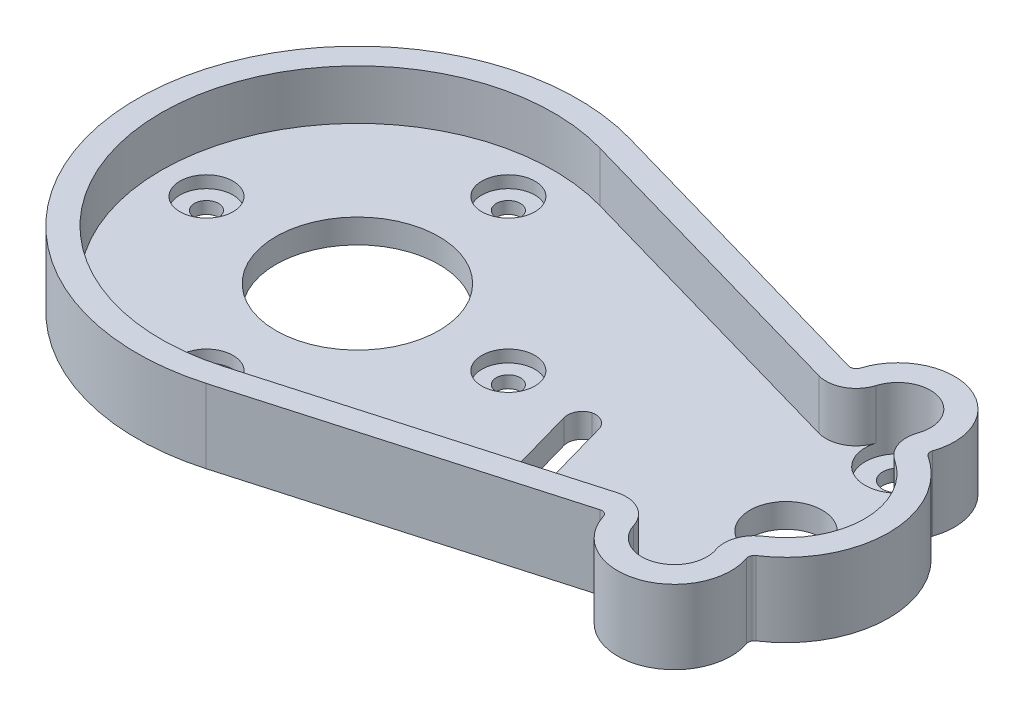
SolidWorks part; units mm, degrees
ref_plane "Front Plane" through (0, 0, 0) normal (0, 0, 1) x (1, 0, 0)
ref_plane "Top Plane" through (0, 0, 0) normal (0, 1, 0) x (1, 0, 0)
ref_plane "Right Plane" through (0, 0, 0) normal (1, 0, 0) x (0, 0, -1)
sketch "Sketch1" plane through (0, 0, 0) normal (0, 1, 0) x (1, 0, 0)
  line L0 (0, 73.0538) -> (0, -65.1274) construction
  line L1 (35.5, 6.365) -> (-28.5632, 24.502) construction
  line L2 (-70.6215, 0) -> (67.3742, 0) construction
  line L3 (35.5, -6.365) -> (-28.5632, -24.502) construction
  line L4 (4.5177, -15.1364) -> (0.1592, 0.2585)
  line L5 (0.1592, 0.2585) -> (4.6815, 1.5388)
  line L6 (4.6815, 1.5388) -> (9.04, -13.8561)
  line L7 (9.04, -13.8561) -> (9.5848, -15.7805)
  line L8 (9.5848, -15.7805) -> (5.0625, -17.0608)
  line L9 (5.0625, -17.0608) -> (4.5177, -15.1364)
  line L10 (-35.5, 0) -> (-60.5, 0) construction
  line L11 (-35.5, 0) -> (-35.5, 25) construction
  line L13 (-87.5, -50) -> (87.5, -50)
  line L14 (-87.5, -50) -> (-87.5, 50)
  line L15 (-87.5, 50) -> (87.5, 50)
  line L16 (87.5, -50) -> (87.5, 50)
  line L17 (-87.5, -50) -> (87.5, 50) construction
  line L18 (-87.5, 50) -> (87.5, -50) construction
  circle A0 centre (35.5, 0) radius 6
  circle A1 centre (-35.5, 0) radius 13.5
  circle A2 centre (-35.5, 0) radius 25.465 construction
  circle A3 centre (35.5, 0) radius 6.365 construction
  circle A4 centre (-60.5, 0) radius 2
  circle A5 centre (-35.5, 25) radius 2
  circle A6 centre (-10.5, 0) radius 2
  circle A7 centre (-35.5, -25) radius 2
  circle A8 centre (35.5, 18.5) radius 2.5
  circle A9 centre (35.5, -18.5) radius 2.5
  point P35 (0, 0)
  dimension "D1" = 12
  dimension "D2" = 27
  dimension "D5" = 50.93
  dimension "D6" = 12.73
  dimension "D12" = 4
  dimension "D19" = 5
  dimension "D3" = 71
  dimension "D4" = 35.5
  dimension "D7" = 90
  dimension "D8" = 27.5
  dimension "D9" = 4.7
  dimension "D10" = 16
  dimension "D11" = 2
  dimension "D13" = 25
  dimension "D15" = 90
  dimension "D16" = 25
  dimension "D17" = 175
  dimension "D18" = 100
  dimension "D20" = 18.5
  dimension "D14" = 4
extrude "Boss-Extrude1" add sketch "Sketch1" along normal blind 4
sketch "Sketch3" plane through (0, 4, 0) normal (0, 1, 0) x (1, 0, 0)
  line L0 (-26.5739, 31.2502) -> (39.0704, 12.5001)
  line L1 (-87.5, -50) -> (87.5, -50)
  line L2 (-87.5, -50) -> (-87.5, 50)
  line L3 (-87.5, 50) -> (87.5, 50)
  line L4 (87.5, -50) -> (87.5, 50)
  line L5 (-35.5, 0) -> (35.5, 0) construction
  line L6 (-26.5739, -31.2502) -> (39.0704, -12.5001)
  arc A0 (-26.5739, 31.2502) -> (-26.5739, -31.2502) centre (-35.5, 0) ccw
  arc A1 (39.0704, -12.5001) -> (39.0704, 12.5001) centre (35.5, 0) ccw
  dimension "D1" = 65
  dimension "D2" = 26
extrude "Boss-Extrude2" add sketch "Sketch3" along normal blind 8.25
sketch "Sketch6" plane through (0, 12.25, 0) normal (0, 1, 0) x (1, 0, 0)
  circle A0 centre (35.5, 18.5) radius 5.4
  circle A1 centre (35.5, -18.5) radius 5.4
  dimension "D1" = 10.8
extrude "Cut-Extrude2" cut sketch "Sketch6" against normal up to surface (8.25 mm away) up to face at (-1.7509, 4, 0)
fillet "Fillet1" radius 2.5 4 edges at (9.5848, 2, 15.7805) (5.0625, 2, 17.0608) (4.6815, 2, -1.5388) (0.1592, 2, -0.2585)
fillet "Fillet2" radius 5 4 edges at (36.5847, 8.125, 13.2101) (31.7849, 8.125, 14.5811) (36.5847, 8.125, -13.2101) (31.7849, 8.125, -14.5811)
sketch "Sketch2" plane through (0, 4, 0) normal (0, 1, 0) x (1, 0, 0)
  line L0 (29.5, 0) -> (41.5, 0) construction
  line L1 (35.5, 0) -> (35.5, -6) construction
  line L2 (35.5, 0) -> (35.5, 6) construction
  circle A0 centre (-35.5, 25) radius 4.4
  circle A1 centre (-10.5, 0) radius 4.4
  circle A2 centre (-35.5, -25) radius 4.4
  circle A3 centre (-60.5, 0) radius 4.4
  circle A4 centre (35.5, 0) radius 6 construction
  circle A7 centre (35.5, 18.5) radius 5.4
  circle A8 centre (35.5, -18.5) radius 5.4
  arc A9 (40.6003, 16.7261) -> (30.3389, 20.0883) centre (35.5, 18.5) ccw construction
  dimension "D1" = 8.8
extrude "Cut-Extrude1" cut sketch "Sketch2" against normal blind 2
sketch "Sketch7" plane through (0, 12.25, 0) normal (0, 1, 0) x (1, 0, 0)
  line L4 (-25.4754, -35.0964) -> (25.2854, -20.5975)
  line L5 (25.2854, 20.5975) -> (-25.4754, 35.0964)
  line L6 (-25.4754, -35.0964) -> (25.2854, -20.5975)
  line L7 (25.2854, 20.5975) -> (-25.4754, 35.0964)
  arc A16 (25.2854, 20.5975) -> (26.5158, 21.2649) centre (25.5601, 21.559) ccw
  arc A17 (44.3783, 15.412) -> (26.5158, 21.2649) centre (35.5, 18.5) ccw
  arc A18 (44.3783, 15.412) -> (44.7771, 14.2455) centre (45.3228, 15.0835) ccw
  arc A19 (44.7771, -14.2455) -> (44.3783, -15.412) centre (45.3228, -15.0835) ccw
  arc A20 (44.7771, -14.2455) -> (44.7771, 14.2455) centre (35.5, 0) ccw
  arc A21 (26.5158, -21.2649) -> (25.2854, -20.5975) centre (25.5601, -21.559) ccw
  arc A22 (26.5158, -21.2649) -> (44.3783, -15.412) centre (35.5, -18.5) ccw
  arc A23 (-25.4754, 35.0964) -> (-25.4754, -35.0964) centre (-35.5, 0) ccw
  arc A24 (25.2854, 20.5975) -> (26.5158, 21.2649) centre (25.5601, 21.559) ccw
  arc A25 (44.3783, 15.412) -> (26.5158, 21.2649) centre (35.5, 18.5) ccw
  arc A26 (44.3783, 15.412) -> (44.7771, 14.2455) centre (45.3228, 15.0835) ccw
  arc A27 (44.7771, -14.2455) -> (44.3783, -15.412) centre (45.3228, -15.0835) ccw
  arc A28 (44.7771, -14.2455) -> (44.7771, 14.2455) centre (35.5, 0) ccw
  arc A29 (26.5158, -21.2649) -> (25.2854, -20.5975) centre (25.5601, -21.559) ccw
  arc A30 (26.5158, -21.2649) -> (44.3783, -15.412) centre (35.5, -18.5) ccw
  arc A31 (-25.4754, 35.0964) -> (-25.4754, -35.0964) centre (-35.5, 0) ccw
  dimension "D1" = 4
extrude "Cut-Extrude4" cut sketch "Sketch7" against normal through all both and the other way through all flip side to cut
